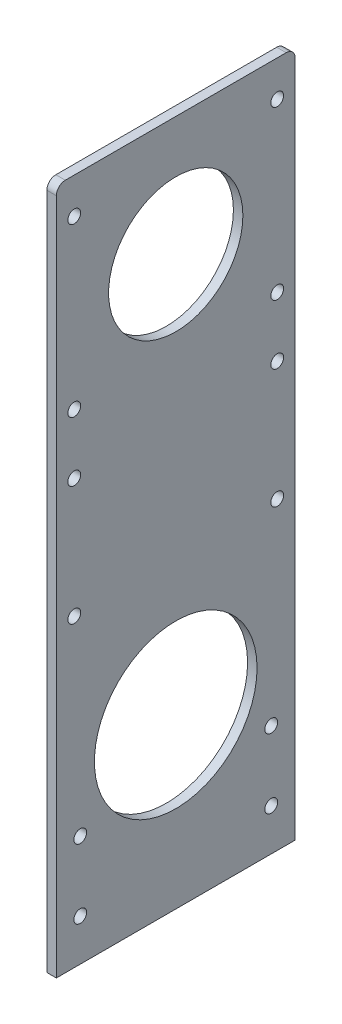
SolidWorks part; units mm, degrees
ref_plane "Front Plane" through (0, 0, 0) normal (0, 0, 1) x (1, 0, 0)
ref_plane "Top Plane" through (0, 0, 0) normal (0, 1, 0) x (1, 0, 0)
ref_plane "Right Plane" through (0, 0, 0) normal (1, 0, 0) x (0, 0, -1)
sketch "Sketch1" plane through (0, 0, 0) normal (1, 0, 0) x (0, 0, -1)
  line L0 (0, 115) -> (0, -115) construction
  line L1 (-40, -115) -> (40, -115)
  line L2 (-40, -115) -> (-40, 115)
  line L3 (-40, 115) -> (40, 115)
  line L4 (40, -115) -> (40, 115)
  line L5 (-40, -115) -> (40, 115) construction
  line L6 (-40, 115) -> (40, -115) construction
  line L7 (-40, 75) -> (40, 75) construction
  circle A0 centre (0, -58.65) radius 27.25
  circle A1 centre (-34, 103) radius 2.15
  circle A2 centre (-34, 47) radius 2.15
  circle A15 centre (34, 47) radius 2.15
  circle A16 centre (34, 103) radius 2.15
  circle A17 centre (0, 75) radius 22.5
  circle A18 centre (-32, -101.025) radius 2.15
  circle A19 centre (32, -101.025) radius 2.15
  circle A24 centre (-32, -77.825) radius 2.15
  circle A25 centre (32, -77.825) radius 2.15
  circle A26 centre (-34, 27) radius 2.15
  circle A27 centre (-34, -13) radius 2.15
  circle A28 centre (34, -13) radius 2.15
  circle A29 centre (34, 27) radius 2.15
  point P0 (0, 0)
  dimension "D4" = 54.5
  dimension "D5" = 4.3
  dimension "D8" = 4.3
  dimension "D6" = 34
  dimension "D10" = 34
  dimension "D12" = 45
  dimension "D13" = 4.3
  dimension "D17" = 4.3
  dimension "D16" = 4.3
  dimension "D1" = 230
  dimension "D2" = 80
  dimension "D3" = 56.35
  dimension "D7" = 12
  dimension "D9" = 56
  dimension "D11" = 28
  dimension "D14" = 8
  dimension "D15" = 13.975
  dimension "D18" = 37.175
  dimension "D19" = 20
  dimension "D20" = 2
extrude "Boss-Extrude1" add sketch "Sketch1" along normal blind 3.175
fillet "Fillet1" radius 3 2 edges at (1.5875, 115, -40) (1.5875, 115, 40)
